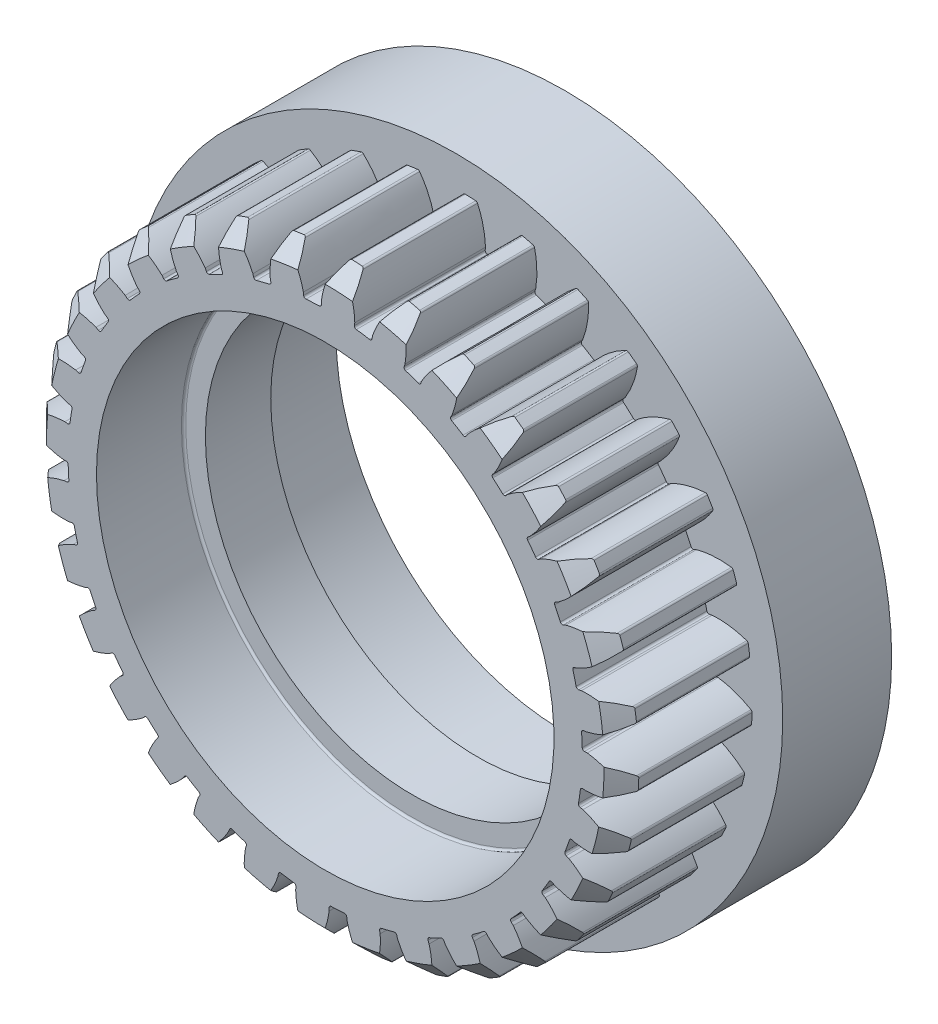
SolidWorks part; units mm, degrees
material "ABS"
ref_plane "Спереди" through (0, 0, 0) normal (0, 0, 1) x (1, 0, 0)
ref_plane "Сверху" through (0, 0, 0) normal (0, 1, 0) x (1, 0, 0)
ref_plane "Справа" through (0, 0, 0) normal (1, 0, 0) x (0, 0, -1)
sketch "Эскиз18" plane through (0, 0, 0) normal (1, 0, 0) x (0, 0, -1)
  line L0 (0, 0) -> (-5.5, 0) construction
  line L2 (-5.5, -10.5) -> (-1.5, -10.5)
  line L3 (-1.5, -10.5) -> (-1.5, -9.5)
  line L4 (-1.5, -9.5) -> (1.5, -9.5)
  line L5 (1.5, -9.5) -> (1.5, -10.5)
  line L6 (1.5, -10.5) -> (5.5, -10.5)
  line L7 (-5.5, -11.8) -> (-5.5, -10.5)
  line L13 (5.5, -15) -> (5.5, -10.5)
  line L14 (0, -9.5) -> (0, -16.579) construction
  line L15 (5.5, -15) -> (0.5, -15)
  line L16 (0.5, -15) -> (0.5, -11.8)
  line L19 (0.5, -11.8) -> (-5.5, -11.8)
  point P11 (0.5, -11.8)
  point P16 (0.5, -11.8695)
  dimension "D2" = 21
  dimension "D5" = 4
  dimension "D9" = 1
  dimension "D4" = 11
  dimension "D1" = 23.6
  dimension "D8" = 30
  dimension "D3" = 6
revolve "Повернуть1" add sketch "Эскиз18" angle 360 about L0
fillet "Скругление2" radius 0.1 2 edges at (-10.5, 0, 1.5) (-10.5, 0, -1.5)
ref_plane "Плоскость1" through (0, 0, 3.5) normal (0, 0, 1) x (1, 0, 0)
sketch "Эскиз19" plane through (0, 0, 3.5) normal (0, 0, 1) x (1, 0, 0)
  line L0 (0, 0) -> (0, 12.8) construction
  line L1 (-1.2398, 12.8) -> (1.2398, 12.8) construction
  line L2 (0, 12.8) -> (4.1138, 11.3027) construction
  line L3 (0.3703, 13.595) -> (5.9011, 10.481) construction
  line L4 (0, 0) -> (-0.1793, 12.0267) construction
  line L5 (-0.1793, 12.0267) -> (-0.1759, 11.7987)
  line L6 (0, 0) -> (0.6673, 13.5836) construction
  line L7 (1.3572, 11.9512) -> (1.3315, 11.7246)
  circle A0 centre (0, 0) radius 11.8 construction
  arc A1 (1.3315, 11.7246) -> (-0.1759, 11.7987) centre (0, 0) ccw
  arc A2 (0.964, 13.5658) -> (0.3703, 13.595) centre (0, 0) ccw
  circle A3 centre (0, 0) radius 12.8 construction
  circle A4 centre (0, 0) radius 12.0281 construction
  spline S0 degree 2 poles (-0.1793, 12.0267) (-0.0686, 12.8674) (0.3703, 13.595) knots 0 0 0 1 1 1
  spline S1 degree 2 poles (1.3572, 11.9512) (1.3295, 12.7987) (0.964, 13.5658) knots 0 0 0 1 1 1
  point P9 (0, 12.8)
  point P17 (-0.1793, 12.0267)
  dimension "D1" = 27.2
  dimension "D2" = 25.6
  dimension "D3" = 20
  dimension "D4" = 4.3779
  dimension "D5" = 6.3471
  dimension "D8" = 2.813
  dimension "D6" = 1.9692
  dimension "D7" = 4.3779
extrude "Бобышка-Вытянуть1" add sketch "Эскиз19" along normal up to surface and the other way up to surface up to face at (-11.8, 0, 5.5) other way up to face at (-15, 0, -0.5)
fillet "Скругление3" radius 0.1 4 edges at (-0.1759, 11.7987, 2.5) (1.3315, 11.7246, 2.5) (0.964, 13.5658, 2.5) (0.3703, 13.595, 2.5)
pattern_circular "Круговой массив1" count 32 over 360 about axis through (0, 0, 0) along (0, 0, -1) of "Бобышка-Вытянуть1", "Скругление3"
sketch "Эскиз21" plane through (0, 0, 0) normal (1, 0, 0) x (0, 0, -1)
  line L0 (-5.5, 0) -> (-5.5, 13.6) construction
  line L1 (-5.5, 0) -> (0.5, 0) construction
  line L2 (-5.5, 1.6658) -> (-5.5, 1.0004) construction
  line L3 (-5.5, 13.6) -> (0.5, 13.6) construction
  line L4 (0.5, 13.6) -> (0.5, 0) construction
  line L6 (1.6, 0) -> (5.5, 0) construction
  line L7 (-5.5, 12.8) -> (0.5, 12.8) construction
  line L8 (-5.5, 12.8) -> (-5.5, 13.6)
  line L9 (-5.5, 13.6) -> (-4.7, 13.6)
  line L10 (-4.7, 13.6) -> (-5.5, 12.8)
  line L15 (0.5, 15) -> (0.5, -15) construction
  point P8 (0.3923, 13.6)
  dimension "D1" = 13.6
  dimension "D2" = 12.8
revolve "Вырез-Повернуть1" cut sketch "Эскиз21" angle 360 about axis through (0, 0, 0) along (0, 0, -1)
equation "\"Модуль\"= 0.8мм"
equation "\"Число зубьев\"= 32"
equation "\"D1@Эскиз18\"= \"Модуль\" * (\"Число зубьев\" - 2.5)"
equation "\"D1@Эскиз19\"= \"Модуль\" * (\"Число зубьев\" + 2)"
equation "\"D2@Эскиз19\"= \"Модуль\" * \"Число зубьев\""
equation "\"D6@Эскиз19\"= \"D5@Эскиз19\" - \"D4@Эскиз19\""
equation "\"D7@Эскиз19\"= \"D4@Эскиз19\""
equation "\"D8@Эскиз19\"= 90 / \"Число зубьев\""
equation "\"D1@Круговой массив1\"= \"Число зубьев\""
equation "\"D1@Эскиз21\"= \"Модуль\" * (\"Число зубьев\" + 2) / 2"
equation "\"D2@Эскиз21\"=\"Модуль\" * \"Число зубьев\" / 2"
